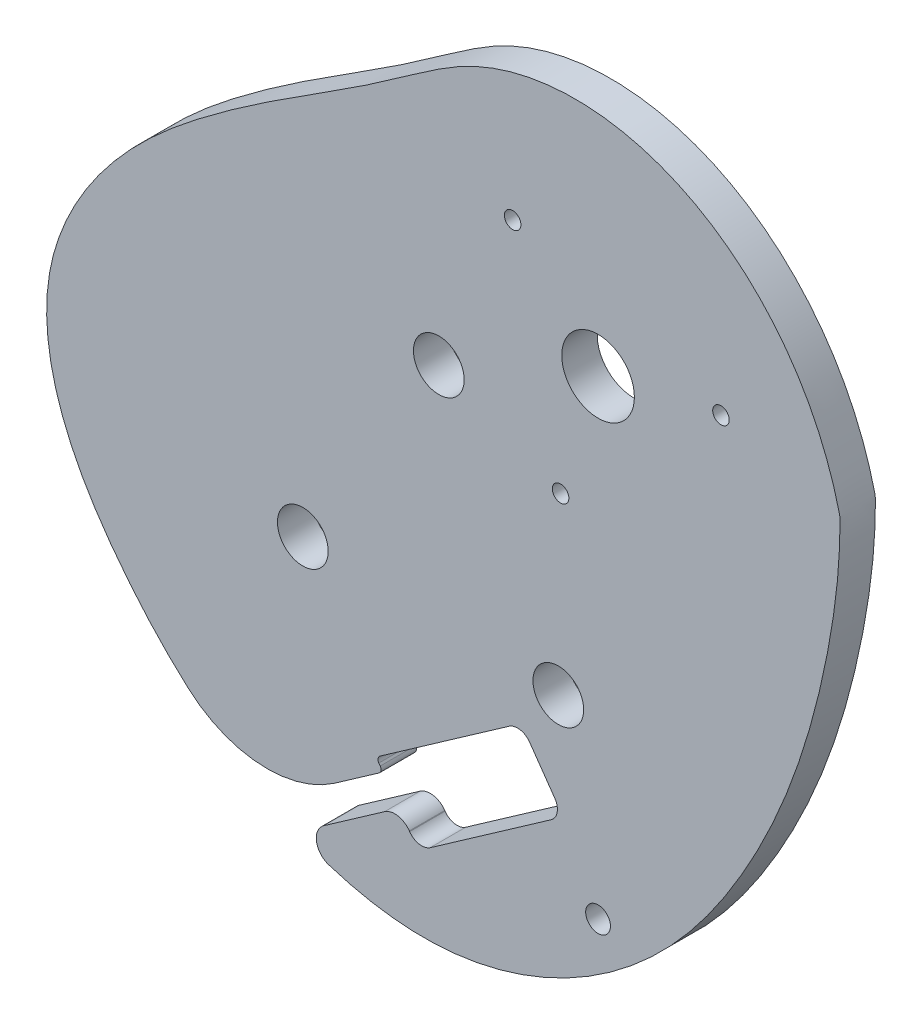
SolidWorks part; units mm, degrees
ref_plane "Front Plane" through (0, 0, 0) normal (0, 0, 1) x (1, 0, 0)
ref_plane "Top Plane" through (0, 0, 0) normal (0, 1, 0) x (1, 0, 0)
ref_plane "Right Plane" through (0, 0, 0) normal (1, 0, 0) x (0, 0, -1)
curve "Curve1"
sketch "Sketch1" plane through (0, 0, 0) normal (0, 0, 1) x (1, 0, 0)
  circle A0 centre (0, 0) radius 3.075
  spline S1 degree 3 number of poles 363 (20.4693, 0) -> (20.4693, 0)
  dimension "D1" = 6.15
extrude "Boss-Extrude1" add sketch "Sketch1" along normal mid plane 3
sketch "Sketch4" plane through (0, 0, 1.5) normal (0, 0, 1) x (1, 0, 0)
  line L0 (17.5773, -21.2942) -> (-0.4059, -51.7692) construction
  line L1 (-48.8051, -15.5697) -> (-20.0826, 24.9009) construction
  circle A0 centre (-13.2083, -15.9321) radius 29.2387 construction
  spline S0 degree 3 number of poles 363 (20.4693, 0) -> (20.4693, 0) construction
  point P5 (-13.488, -5.936)
  point P6 (-3.3675, -25.0764)
  point P11 (-25.0038, -24.2708)
  point P12 (-13.9531, -18.4277)
  dimension "D1" = 3
  dimension "D2" = 10
hole_wizard "M4 Clearance Hole1" positions "Sketch5" profile "Sketch7" hole size "M4" standard "ANSI Metric" end condition through all
sketch "Sketch5" plane through (0, 0, 1.5) normal (0, 0, 1) x (1, 0, 0)
  point P0 (-13.488, -5.936)
  point P3 (-3.3675, -25.0764)
  point P6 (-25.0038, -24.2708)
sketch "Sketch7" plane through (-13.488, -5.936, 1.5) normal (1, 0, 0) x (0, -1, 0)
  line L0 (0, 0) -> (0, 3)
  line L1 (0, 3) -> (2.15, 3)
  line L2 (2.15, 3) -> (2.15, 0)
  line L5 (2.15, 0) -> (0, 0)
  line L11 (0, -6.35) -> (0, 107.95) construction
  dimension "Thru Hole Dia." = 4.3
  dimension "Thru Hole Depth" = 3
sketch "Sketch8" plane through (0, 0, 1.5) normal (0, 0, 1) x (1, 0, 0)
  line L5 (-11.09, -40.8947) -> (-20.9198, -47.7776) construction
  line L8 (-28.4462, -45.3019) -> (-27.0696, -47.2679)
  line L9 (-15.2394, -42.4024) -> (-16.8454, -40.1088)
  line L10 (-16.8454, -40.1088) -> (-27.0696, -47.2679)
  line L11 (-6.9178, -29.0068) -> (-3.3617, -34.0855) construction
  line L13 (-6.9178, -29.0068) -> (-18.7955, -37.3237)
  line L15 (-15.2394, -42.4024) -> (-3.3617, -34.0855)
  line L16 (-18.7955, -37.3237) -> (-18.222, -38.1428)
  line L17 (-18.222, -38.1428) -> (-28.4462, -45.3019)
  line L18 (-6.9178, -29.0068) -> (-6.5083, -28.72)
  line L19 (-6.5083, -28.72) -> (-2.9521, -33.7988)
  line L22 (-3.3617, -34.0855) -> (-2.9521, -33.7988)
  spline S1 degree 3 number of poles 363 (20.4693, 0) -> (20.4693, 0) construction
  dimension "D6" = 2.4
  dimension "D1" = 14.5
  dimension "D2" = 2.8
  dimension "D3" = 12
  dimension "D4" = 0.5
  dimension "D8" = 27
  dimension "D9" = 14.5
  dimension "D10" = 6.2
  dimension "D11" = 1
extrude "Cut-Extrude1" cut sketch "Sketch8" against normal through all both and the other way through all
fillet "Fillet1" radius 10 1 edges at (-28.0014, -44.9905, 0)
sketch "Sketch10" [suppressed] plane through (0, 0, 0) normal (0, 0, 1) x (1, 0, 0)
  line L1 (-8.5177, -31.4464) -> (-10.3214, -44.6038) construction
  line L2 (-22.8408, -43.8925) -> (-20.9018, -29.7487) construction
  line L3 (-8.5177, -31.4464) -> (-10.3214, -44.6038)
  line L4 (-22.8408, -43.8925) -> (-20.9018, -29.7487)
  circle A6 centre (-13.0442, -46.0588) radius 1.5
  arc A7 (-10.3214, -44.6038) -> (-7.077, -47.3226) centre (-7.8445, -44.9433) ccw construction
  arc A8 (-8.5177, -31.4464) -> (-20.9018, -29.7487) centre (-14.7098, -30.5976) ccw construction
  arc A9 (-26.388, -45.8122) -> (-22.8408, -43.8925) centre (-25.3176, -43.5529) ccw construction
  arc A10 (-10.3214, -44.6038) -> (-7.077, -47.3226) centre (-7.8445, -44.9433) ccw
  arc A11 (-8.5177, -31.4464) -> (-20.9018, -29.7487) centre (-14.7098, -30.5976) ccw
  arc A12 (-26.388, -45.8122) -> (-22.8408, -43.8925) centre (-25.3176, -43.5529) ccw
  spline S1 degree 3 number of poles 363 (-7.077, -47.3226) -> (-26.388, -45.8122) construction
  spline S2 degree 3 number of poles 213 (-7.077, -47.3226) -> (-26.388, -45.8122)
  spline S4 degree 3 number of poles 165 (-53.4212, -32.1303) -> (-53.4212, -32.1303)
  spline S5 degree 3 number of poles 165 (-53.4212, -32.1303) -> (-53.4212, -32.1303)
  dimension "D2" = 3
  dimension "D3" = 2.5
  dimension "D1" = 10
extrude "Boss-Extrude5" [suppressed] add sketch "Sketch10" along normal mid plane 1.5
sketch "Sketch11" plane through (0, 0, 0) normal (0, 0, 1) x (1, 0, 0)
  point P0 (-7.234, 7.8407)
  point P1 (10.4072, 2.3444)
  point P3 (-3.1732, -10.1851)
hole_wizard "M2x0.4 Tapped Hole1" positions "Sketch12" profile "Sketch13" tap size "M2x0.4" standard "ANSI Metric" end condition through all
sketch "Sketch12" plane through (0, 0, -1.5) normal (0, 0, -1) x (-1, 0, 0)
  point P0 (7.234, 7.8407)
  point P3 (-10.4072, 2.3444)
  point P6 (3.1732, -10.1851)
sketch "Sketch13" plane through (-7.234, 7.8407, -1.5) normal (1, 0, 0) x (0, 1, 0)
  line L0 (0, 0) -> (0, 3)
  line L1 (0, 3) -> (0.7, 3)
  line L2 (0.7, 3) -> (0.7, 0)
  line L5 (0.7, 0) -> (0, 0)
  line L11 (0, -6.35) -> (0, 107.95) construction
  dimension "Thru Tap Drill Dia." = 1.4
  dimension "Thru Tap Drill Depth" = 3
cosmetic thread "Hole Thread1" parameters "D2"=2
cosmetic thread "Hole Thread2" parameters "D2"=2
cosmetic thread "Hole Thread3" parameters "D2"=2
fillet "Fillet2" radius 1.5 2 edges at (-25.5415, -46.1978, 0) (-16.8454, -40.1088, 0)
sketch "Sketch14" plane through (0, 0, 1.5) normal (0, 0, 1) x (1, 0, 0)
  circle A0 centre (-12.5246, -41.0492) radius 1.05 construction
  circle A1 centre (0, -39.819) radius 1.05
  dimension "D1" = 2.1
  dimension "D2" = 2.1
extrude "Cut-Extrude2" cut sketch "Sketch14" against normal through all
sketch "Sketch15" [suppressed] plane through (0, 0, 0.75) normal (0, 0, 1) x (1, 0, 0)
  circle A0 centre (-24.2994, -39.0947) radius 1.1
  circle A1 centre (-14.3282, -44.0575) radius 1.1
extrude "Cut-Extrude3" [suppressed] cut sketch "Sketch15" against normal blind 10
sketch "Sketch16" [suppressed] plane through (0, 0, 0.75) normal (0, 0, 1) x (1, 0, 0)
  circle A0 centre (-5.523, -52.2474) radius 1.15
  circle A1 centre (5.4449, -44.5935) radius 1.15
  dimension "D1" = 2.3
  dimension "D2" = 2.3
extrude "Cut-Extrude4" [suppressed] cut sketch "Sketch16" against normal blind 10
fillet "Fillet3" radius 0.4 2 edges at (-18.222, -38.1428, 0) (-18.7955, -37.3237, 0)
fillet "Fillet4" radius 1.25 3 edges at (-2.9521, -33.7988, 0) (-6.5083, -28.72, 0) (-15.2394, -42.4024, 0)
